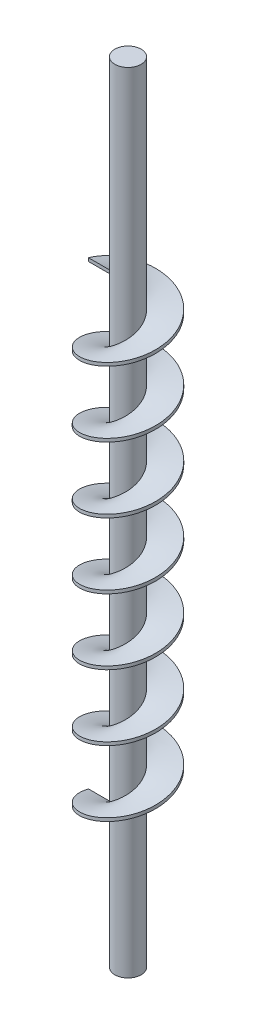
SolidWorks part; units mm, degrees
ref_plane "Front Plane" through (0, 0, 0) normal (0, 0, 1) x (1, 0, 0)
ref_plane "Top Plane" through (0, 0, 0) normal (0, 1, 0) x (1, 0, 0)
ref_plane "Right Plane" through (0, 0, 0) normal (1, 0, 0) x (0, 0, -1)
sketch "Sketch1" plane through (0, 0, 0) normal (0, 1, 0) x (1, 0, 0)
  circle A0 centre (0, 0) radius 4
  dimension "D1" = 8
extrude "Boss-Extrude1" add sketch "Sketch1" along normal blind 200
sketch "Sketch3" plane through (0, 0, 0) normal (0, -1, 0) x (1, 0, 0)
  circle A0 centre (0, 0) radius 10
curve "Helix/Spiral1" pitch 20 height 140 radius 10 centre (0, 0, 0) axis (0, 1, 0) start towards (0, 0, -1)
sketch "Sketch4" plane through (0, 0, 0) normal (0, 0, 1) x (1, 0, 0)
  line L0 (-4, 0) -> (-12, 0)
  line L1 (-12, 0) -> (-12, 1)
  line L2 (-12, 1) -> (-4, 1)
  line L3 (-4, 200) -> (-4, 0) construction
  line L4 (-4, 1) -> (-4, 0)
  dimension "D1" = 12
  dimension "D2" = 1
sweep "Sweep1" add profiles "Sketch4" path "Helix/Spiral1"
sketch "Sketch6" plane through (0, 0, 0) normal (0, -1, 0) x (1, 0, 0)
  circle A1 centre (0, 0) radius 4
  circle A2 centre (0, 0) radius 4
  dimension "D1" = 0
extrude "Boss-Extrude2" add sketch "Sketch6" along normal blind 40
